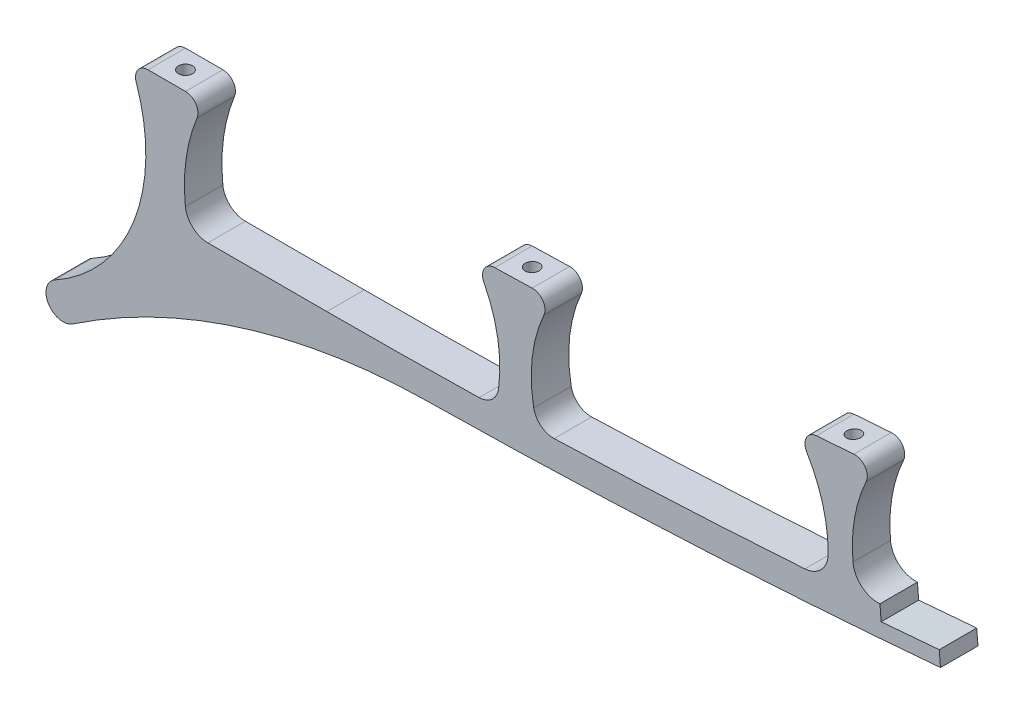
SolidWorks part; units mm, degrees
ref_plane "Front Plane" through (0, 0, 0) normal (0, 0, 1) x (1, 0, 0)
ref_plane "Top Plane" through (0, 0, 0) normal (0, 1, 0) x (1, 0, 0)
ref_plane "Right Plane" through (0, 0, 0) normal (1, 0, 0) x (0, 0, -1)
sketch "Sketch1" plane through (0, 0, 4.0971) normal (0, 0, -1) x (-1, 0, 0)
  line L0 (-62.7619, -51.7222) -> (-58.001, -51.5972) construction
  line L1 (-62.7619, -51.7222) -> (-58.001, -51.5972)
  line L2 (-250.1152, -63.0874) -> (-250.684, -56.8905) construction
  line L3 (-250.1152, -63.0874) -> (-250.684, -56.8905)
  line L4 (5.0134, -50.6875) -> (4.8506, -13.0704)
  line L5 (293.8258, -32.3629) -> (292.5411, -55.9947)
  line L6 (459.2981, -30.7507) -> (468.8231, -30.7507)
  line L7 (423.3798, -61.2307) -> (453.91, -61.2307)
  line L10 (423.2417, -37.1007) -> (607.4086, -37.1007) construction
  line L11 (270.0646, -24.076) -> (423.3798, -30.7507) construction
  line L12 (269.6518, -30.414) -> (423.1036, -37.0947) construction
  line L13 (270.0646, -24.076) -> (423.3798, -30.7507) construction
  line L14 (269.6518, -30.414) -> (423.2417, -37.1007) construction
  line L15 (270.0646, -24.076) -> (423.3798, -30.7507) construction
  line L16 (268.1133, -54.0366) -> (422.0742, -60.7394) construction
  line L17 (268.1133, -54.0366) -> (282.8559, -55.2703)
  line L39 (464.0606, -30.7507) -> (464.0606, -61.2307)
  line L43 (423.3798, -61.2307) -> (607.4086, -61.2307) construction
  line L44 (375.9837, -30.118) -> (375.1663, -60.587)
  line L45 (423.3798, -30.7507) -> (607.4086, -30.7507) construction
  arc A10 (295.9963, -50.7756) -> (301.9161, -57.1188) centre (302.3463, -50.7834) ccw
  arc A11 (301.4662, -31.1688) -> (298.9719, -26.3615) centre (298.7477, -29.5285) ccw
  arc A12 (289.4896, -25.6646) -> (286.3657, -30.1613) centre (289.2483, -28.8304) ccw
  arc A13 (282.8559, -55.2703) -> (289.7096, -49.5155) centre (283.3855, -48.9424) ccw
  arc A17 (301.4662, -31.1688) -> (295.9963, -50.7756) centre (334.0387, -50.8222) ccw
  arc A18 (289.7096, -49.5155) -> (286.3657, -30.1613) centre (251.8722, -46.0867) ccw
  circle A19 centre (490.3927, -92.6507) radius 4.3495
  arc A24 (383.4811, -34.8689) -> (379.749, -56.3925) centre (415.8403, -51.5652) ccw
  circle A29 centre (384.8064, -55.7161) radius 5.1024
  arc A30 (471.8244, -34.9614) -> (468.8231, -30.7507) centre (468.8231, -33.9257) ccw
  arc A31 (459.2981, -30.7507) -> (456.3562, -35.1198) centre (459.2981, -33.9257) ccw
  circle A32 centre (453.6208, -55.4881) radius 5.7427
  arc A33 (383.4811, -34.8689) -> (380.7361, -30.239) centre (380.6595, -33.4131) ccw
  arc A36 (459.3328, -56.0812) -> (456.3562, -35.1198) centre (415.8403, -51.5652) ccw
  arc A39 (368.2424, -34.4601) -> (371.2316, -29.9841) centre (371.1379, -33.1577) cw
  arc A40 (368.2424, -34.4601) -> (370.815, -56.1528) centre (335.0345, -49.3973) cw
  circle A41 centre (365.8012, -55.2062) radius 5.1024
  arc A42 (487.9615, -96.2573) -> (398.3517, -68.1968) centre (396.0818, -232.558) ccw
  arc A43 (471.8244, -34.9614) -> (492.4999, -88.8458) centre (514.2362, -49.5967) ccw
  spline S20 degree 1 poles (366398.024, 9576.3228) (-366524.7965, -9679.8002) knots -76971.699337 -76971.699337 76975.961644 76975.961644 only from (-53.2401, -51.4722) to (-58.001, -51.5972) construction
  spline S21 degree 1 poles (-53.2401, -51.4722) (-58.001, -51.5972) knots 0 0 1 1
  spline S22 degree 3 poles (-366283.8205, -17716.948) (-122202.6297, -5946.5803) (121970.8169, 5839.1835) (366052.004, 17609.5507) knots -76977.855707 -76977.855707 -76977.855707 -76977.855707 76982.000972 76982.000972 76982.000972 76982.000972 only from (-125.7663, -54.1741) to (-121.0093, -53.9446) construction
  spline S23 degree 1 poles (366035.5792, 17611.4947) (-366288.3596, -17719.9032) knots -76971.699337 -76971.699337 76975.961644 76975.961644 only from (-116.2524, -53.7151) to (-121.0093, -53.9446) construction
  spline S24 degree 3 poles (-125.7663, -54.1741) (-124.1807, -54.0976) (-122.595, -54.0211) (-121.0093, -53.9446) knots 0 0 0 0 1 1 1 1
  spline S25 degree 1 poles (-116.2524, -53.7151) (-121.0093, -53.9446) knots 0 0 1 1
  spline S26 degree 3 poles (-365864.3718, -25779.0387) (-122073.8662, -8605.5374) (121716.5905, 8490.9359) (365507.0964, 25664.4407) knots -76971.699337 -76971.699337 -76971.699337 -76971.699337 76975.961644 76975.961644 76975.961644 76975.961644 only from (-188.7625, -58.0119) to (-184.0117, -57.678) construction
  spline S27 degree 1 poles (365496.3363, 25644.4265) (-365875.1074, -25760.538) knots -76971.699337 -76971.699337 76975.961644 76975.961644 only from (-179.2609, -57.3441) to (-184.0117, -57.678) construction
  spline S28 degree 3 poles (-188.7625, -58.0119) (-187.1789, -57.9006) (-185.5953, -57.7893) (-184.0117, -57.678) knots 0 0 0 0 1 1 1 1
  spline S29 degree 1 poles (-179.2609, -57.3441) (-184.0117, -57.678) knots 0 0 1 1
  spline S30 degree 3 poles (-365301.3101, -33565.7342) (-121968.4672, -11235.1782) (121487.2779, 11110.751) (364820.1161, 33441.3066) knots -76979.795154 -76979.795154 -76979.795154 -76979.795154 76983.809836 76983.809836 76983.809836 76983.809836 only from (-250.1152, -63.0874) to (-245.3727, -62.6521) construction
  spline S31 degree 1 poles (364802.8942, 33440.7494) (-365304.3687, -33567.0383) knots -76971.699337 -76971.699337 76975.961644 76975.961644 only from (-240.6301, -62.2168) to (-245.3727, -62.6521) construction
  spline S32 degree 3 poles (-250.1152, -63.0874) (-248.5344, -62.9423) (-246.9535, -62.7972) (-245.3727, -62.6521) knots 0 0 0 0 1 1 1 1
  spline S33 degree 1 poles (-240.6301, -62.2168) (-245.3727, -62.6521) knots 0 0 1 1
  spline S34 degree 3 poles (-351120.2294, 74427.9388) (10494.0217, 34620.9522) (5972.352, 298.9935) (-6644.5567, -363.006) (-14732.5977, 33292.3398) (340712.2066, 110676.7005) knots -40.409558 -40.409558 -40.409558 -40.409558 0.498012 0.498012 41.40254 41.40254 41.40254 41.40254 only from (-260.2582, -26.3703) to (-413.5099, -34.3711) construction
  spline S35 degree 3 poles (-260.2582, -26.3703) (-285.573, -28.8027) (-310.9405, -30.6861) (-362.0399, -33.3672) (-387.7725, -34.1516) (-413.5099, -34.3711) knots 0.333333 0.333333 0.333333 0.333333 0.498012 0.498012 0.664679 0.664679 0.664679 0.664679
  spline S36 degree 3 poles (350477.0671, 77415.5224) (-10783.169, 34525.5553) (-5964.8095, 247.3458) (6657.3809, -305.4861) (14454.3598, 33422.1949) (-341643.6335, 107772.7294) knots -40.405514 -40.405514 -40.405514 -40.405514 0.5 0.5 41.406764 41.406764 41.406764 41.406764 only from (270.0646, -24.076) to (423.3798, -30.7507) construction
  spline S37 degree 3 poles (270.0646, -24.076) (295.3995, -26.2893) (320.7823, -27.9531) (371.903, -30.1921) (397.6415, -30.7539) (423.3798, -30.7507) knots 0.335321 0.335321 0.335321 0.335321 0.5 0.5 0.666667 0.666667 0.666667 0.666667
  spline S38 degree 3 poles (34216.6622, 363348.8873) (5327.7801, -4762.6903) (2936.3737, -226.3591) (225.9514, -20.5338) (214.915, -19.7614) (181.7932, -17.6233) (159.6926, -16.4536) (115.476, -14.6188) (93.3552, -13.9534) (60.1689, -13.3398) (49.1062, -13.195) (-2720.7868, 6.5962) (-5526.344, -4450.3222) (-4429.285, 364973.5107) knots -30.461707 -30.461707 -30.461707 -30.461707 0.125 0.125 0.25 0.25 0.5 0.5 0.75 0.75 0.875 0.875 32.045674 32.045674 32.045674 32.045674 only from (270.0646, -24.076) to (4.8506, -13.0704) construction
  spline S39 degree 3 poles (-37282.4943, 363051.1607) (-5277.6718, -4808.7913) (-2924.7638, -251.7198) (-216.1773, -22.4465) (-205.1481, -21.5787) (-172.0462, -19.1541) (-149.9564, -17.7933) (-105.7573, -15.5759) (-83.6432, -14.7191) (-50.4634, -13.8184) (-39.4023, -13.5779) (2730.1506, 30.1779) (5573.6801, -4402.0973) (1314.8646, 364983.8749) knots -30.462296 -30.462296 -30.462296 -30.462296 0.125 0.125 0.25 0.25 0.5 0.5 0.75 0.75 0.875 0.875 32.044896 32.044896 32.044896 32.044896 only from (-260.2582, -26.3703) to (4.8506, -13.0704) construction
  spline S40 degree 3 poles (270.0646, -24.076) (259.0414, -23.1193) (248.0148, -22.2092) (225.9514, -20.5338) (214.915, -19.7614) (181.7932, -17.6233) (159.6926, -16.4536) (115.476, -14.6188) (93.3552, -13.9534) (60.1689, -13.3398) (49.1062, -13.195) (26.9794, -13.0369) (15.9153, -13.0299) (4.8506, -13.0704) knots 0 0 0 0 0.125 0.125 0.25 0.25 0.5 0.5 0.75 0.75 0.875 0.875 1 1 1 1
  spline S41 degree 3 poles (-260.2582, -26.3703) (-249.2437, -25.3183) (-238.2254, -24.3128) (-216.1773, -22.4465) (-205.1481, -21.5787) (-172.0462, -19.1541) (-149.9564, -17.7933) (-105.7573, -15.5759) (-83.6432, -14.7191) (-50.4634, -13.8184) (-39.4023, -13.5779) (-17.2777, -13.2284) (-6.214, -13.1256) (4.8506, -13.0704) knots 0 0 0 0 0.125 0.125 0.25 0.25 0.5 0.5 0.75 0.75 0.875 0.875 1 1 1 1
  spline S42 degree 1 poles (266.8016, -61.5516) (423.3844, -68.3681) knots 0 0 1 1 construction
  spline S43 degree 1 poles (266.8016, -61.5516) (5.0134, -50.6875) knots 0 0 1 1 construction
  spline S44 degree 1 poles (-256.671, -63.8163) (5.0134, -50.6875) knots 0 0 1 1 construction
  spline S45 degree 1 poles (-256.671, -63.8163) (-413.1891, -71.9871) knots 0 0 1 1 construction
  spline S46 degree 3 poles (423.3844, -68.3681) (417.128, -68.3689) (406.6951, -68.3157) (354.4413, -67.5941) (308.4593, -65.1906) (266.8016, -61.5516) knots 0.335344 0.335344 0.335344 0.335344 0.375021 0.401473 0.666667 0.666667 0.666667 0.666667
  spline S47 degree 3 poles (266.8016, -61.5516) (261.3509, -61.0786) (250.4335, -60.154) (228.7012, -58.4345) (190.549, -55.7631) (136.0425, -52.8693) (81.4825, -51.2368) (43.241, -50.7379) (21.4384, -50.6506) (10.4839, -50.6675) (5.0134, -50.6875) knots 0.00004 0.00004 0.00004 0.00004 0.062532 0.125024 0.250007 0.499973 0.749939 0.874922 0.937414 0.999905 0.999905 0.999905 0.999905
  spline S48 degree 3 poles (5.0134, -50.6875) (-0.4572, -50.7148) (-11.4114, -50.7928) (-33.2124, -51.0686) (-71.4483, -51.8985) (-125.9921, -54.0029) (-180.4716, -57.3683) (-218.5991, -60.3696) (-240.3157, -62.2771) (-251.2247, -63.2961) (-256.671, -63.8163) knots 0.00004 0.00004 0.00004 0.00004 0.062532 0.125023 0.250007 0.499973 0.749939 0.874922 0.937414 0.999905 0.999905 0.999905 0.999905
  spline S49 degree 3 poles (-256.671, -63.8163) (-308.6753, -68.8128) (-360.9473, -71.5416) (-413.1891, -71.9871) knots 0.333356 0.333356 0.333356 0.333356 0.664679 0.664679 0.664679 0.664679
  spline S50 degree 1 poles (267.412, -54.4403) (423.3798, -61.2307) knots 0 0 1 1 construction
  spline S51 degree 1 poles (268.1133, -54.0366) (4.9805, -43.0872) knots 0 0 1 1 construction
  spline S52 degree 1 poles (-257.3958, -56.2506) (4.9805, -43.0872) knots 0 0 1 1 construction
  spline S53 degree 1 poles (-257.3958, -56.2506) (-413.254, -64.3871) knots 0 0 1 1 construction
  spline S54 degree 3 poles (267.412, -54.4403) (276.0285, -55.1931) (290.4062, -56.3442) (313.5674, -57.917) (336.8899, -59.2149) (356.0529, -59.9983) (367.2252, -60.3576) (370.4015, -60.4534) (373.5779, -60.5449) (376.7545, -60.6301) (379.9313, -60.709) (383.1082, -60.7837) (397.5889, -61.095) (411.2827, -61.2322) (423.3798, -61.2307) knots 0.335321 0.335321 0.335321 0.335321 0.390393 0.427108 0.483088 0.539068 0.549181 0.554238 0.559295 0.569408 0.574465 0.579521 0.589635 0.666659 0.666659 0.666659 0.666659 only from (301.9161, -57.1188) to (423.3798, -61.2307)
  spline S55 degree 3 poles (268.1133, -54.0366) (262.6347, -53.5611) (251.6633, -52.6287) (229.8118, -50.8954) (191.4718, -48.2039) (136.6796, -45.2869) (81.8357, -43.6415) (43.4028, -43.1385) (21.4808, -43.0503) (10.477, -43.0671) (4.9805, -43.0872) knots -0.002434 -0.002434 -0.002434 -0.002434 0.060213 0.122861 0.248155 0.498745 0.749335 0.87463 0.937277 0.999924 0.999924 0.999924 0.999924
  spline S56 degree 3 poles (4.9805, -43.0872) (-0.5025, -43.1146) (-11.479, -43.1927) (-33.3456, -43.4694) (-71.6781, -44.3013) (-126.3714, -46.4114) (-181.0006, -49.7861) (-219.224, -52.795) (-241.0064, -54.7082) (-251.9372, -55.7293) (-257.3958, -56.2506) knots 0.000032 0.000032 0.000032 0.000032 0.062525 0.125019 0.250005 0.499978 0.749951 0.874938 0.937431 0.999924 0.999924 0.999924 0.999924
  spline S57 degree 3 poles (-257.3958, -56.2506) (-309.1808, -61.2261) (-361.2324, -63.9435) (-413.254, -64.3871) knots 0.333351 0.333351 0.333351 0.333351 0.664679 0.664679 0.664679 0.664679
  spline S59 degree 3 poles (-413.1844, -71.9874) (-456.1014, -80.1224) (-434.4954, -79.3287) (-479.9907, -101.3371) (-478.4868, -100.9323) knots 0 0 0 0 0.938514 1 1 1 1
  spline S61 degree 1 poles (269.6518, -30.414) (4.8739, -19.4204) knots 0 0 1 1 construction
  spline S63 degree 3 poles (4.8739, -19.4204) (26.9656, -19.3394) (71.1539, -19.6344) (137.3995, -21.6337) (203.5831, -25.1323) (247.6429, -28.5039) (269.6518, -30.414) knots -0.000515 -0.000515 -0.000515 -0.000515 0.249614 0.499743 0.749871 1 1 1 1
  spline S66 degree 1 poles (269.6518, -30.414) (4.8739, -19.4204) knots 0 0 1 1 construction
  spline S68 degree 3 poles (4.8739, -19.4204) (26.9656, -19.3394) (71.1539, -19.6344) (137.3995, -21.6337) (203.5831, -25.1323) (247.6429, -28.5039) (269.6518, -30.414) knots -0.000515 -0.000515 -0.000515 -0.000515 0.249614 0.499743 0.749871 1 1 1 1
  point P81 (310.3019, -33.4897)
  dimension "D3" = 30.48
  dimension "D5" = 6.35
  dimension "D8" = 4.7625
  dimension "D9" = 3.175
  dimension "D10" = 9.525
  dimension "D11" = 12.7
  dimension "D12" = 19.05
  dimension "D16" = 12.7
  dimension "D17" = 3.175
  dimension "D18" = 4.7625
  dimension "D19" = 4.7625
  dimension "D13" = 9.525
  dimension "D14" = 4.7625
  dimension "D15" = 25.4
  dimension "D1" = 37.6174
  dimension "D7" = 6.35
  dimension "D22" = 6.35
extrude "Boss-Extrude5" add sketch "Sketch1" along normal blind 4.7625 and the other way blind 4.7625 contours L7 S54 A10 A17 A11 S37 A12 A18 A13 L17 S55 | A19 | A19 | S54 L44 S37 | L44 S54 A29 A24 A33 S37 region at (-287.273, -56.7987, 4.0971) region at (-490.3927, -92.6507, 4.0971) region at (-372.7453, -43.9651, 4.0971) region at (-378.475, -44.1188, 4.0971)
ref_plane "Plane1" through (0.3209, -4.3662, 0) normal (-0.0733, 0.9973, 0) x (0.9973, 0.0733, 0)
sketch "Sketch6" plane through (0.3209, -4.3662, 0) normal (-0.0733, 0.9973, 0) x (0.9973, 0.0733, 0)
  line L0 (-295.346, 0.6654) -> (-295.346, -8.8596) construction
  line L1 (-290.592, -4.0971) -> (-300.0999, -4.0971) construction
  line L4 (-290.592, -8.8596) -> (-290.592, 0.6654)
  line L10 (-300.0999, 0.6654) -> (-300.0999, -8.8596)
  line L24 (-290.592, -8.8596) -> (-290.592, 0.6654)
  line L27 (-290.592, 0.6654) -> (-300.0999, 0.6654)
  line L29 (-290.592, 0.6654) -> (-300.0999, 0.6654)
  line L30 (-300.0999, -8.8596) -> (-290.592, -8.8596)
  line L31 (-300.0999, -8.8596) -> (-290.592, -8.8596)
  line L34 (-300.0999, 0.6654) -> (-300.0999, -8.8596)
  circle A0 centre (-295.346, -4.0971) radius 1.778
  point P6 (-290.592, -4.0971)
  point P7 (-295.346, 0.6654)
  point P12 (0, 0)
  point P13 (-295.346, -4.0971)
  dimension "D1" = 0
extrude "Cut-Extrude3" cut sketch "Sketch6" against normal through all contours A0
ref_axis "Axis1" through (-291.4807, -63.4328, 4.0971) along (-0.0733, 0.9973, 0)
ref_plane "Plane2" through (3.0659, -41.7188, 0) normal (-0.0733, 0.9973, 0) x (-0.9947, -0.0731, 0.0729)
sketch "Sketch7" plane through (3.0659, -41.7188, 0) normal (-0.0733, 0.9973, 0) x (-0.9947, -0.0731, 0.0729)
  circle A0 centre (294.8582, -17.4541) radius 1.778 construction
  circle A1 centre (294.8582, -17.4541) radius 1.778
  circle A2 centre (294.8582, -17.4541) radius 3.048
  dimension "D1" = 6.096
extrude "Cut-Extrude4" cut sketch "Sketch7" along normal blind 3.556 and the other way through all
mirror "Mirror4" about plane through (-4.794, 0.0207, 8.8596) normal (-1, 0.0043, 0) of "Cut-Extrude4", "Cut-Extrude3", "Boss-Extrude5"
sketch "Sketch8" plane through (0, 0, -0.6654) normal (0, 0, -1) x (-1, 0, 0)
  line L0 (-4352.3873, -105.2388) -> (-4674.1378, -106.5977)
  line L1 (-4352.3873, -105.2388) -> (-4352.7091, -29.0388)
  line L2 (-4674.1378, -106.5977) -> (-4674.4596, -30.3977)
  line L3 (-4352.7091, -29.0388) -> (-4674.4596, -30.3977)
  dimension "D1" = 76.2
  dimension "D2" = 321.7505
sketch "Sketch9" plane through (0, 0, -0.6654) normal (0, 0, -1) x (-1, 0, 0)
  line L0 (268.1133, -54.0366) -> (282.8559, -55.2703) construction
  line L1 (268.1133, -54.0366) -> (282.8559, -55.2703)
  line L2 (267.7955, -57.8333) -> (282.5382, -59.067)
  line L3 (282.5382, -59.067) -> (282.8559, -55.2703)
  line L4 (267.7955, -57.8333) -> (267.4671, -61.6096)
  line L5 (268.1133, -54.0366) -> (271.2267, -16.8305)
  line L6 (271.2267, -16.8305) -> (-501.7302, -16.8305)
  line L7 (-501.7302, -16.8305) -> (-501.7302, -147.1798)
  line L8 (-501.7302, -147.1798) -> (267.4671, -61.6096)
  spline S0 degree 3 poles (2340.1552, 397.7315) (1297.6129, 87.0856) (115.0439, -338.026) (-1058.2174, 398.7267) (-1032.0079, 1250.0528) knots -2.465055 -2.465055 -2.465055 -2.465055 0.401473 5.010775 5.010775 5.010775 5.010775 only from (398.3517, -68.1968) to (266.8016, -61.5516) construction
  spline S1 degree 3 poles (398.3517, -68.1968) (396.2658, -68.168) (352.3561, -67.4851) (308.4593, -65.1906) (266.8016, -61.5516) knots 0.388247 0.388247 0.388247 0.388247 0.401473 0.666667 0.666667 0.666667 0.666667
  dimension "D1" = 3.81
extrude "Cut-Extrude5" cut sketch "Sketch9" against normal through all contours L7 L8 L4 L2 L3 L1 L5 L6 region at (178.8306, -64.0501, -0.6654)
ref_plane "Plane3" through (0.5368, -20.0102, 0) normal (-0.0268, 0.9996, 0) x (0.9996, 0.0268, 0)
sketch "Sketch10" plane through (0.5368, -20.0102, 0) normal (-0.0268, 0.9996, 0) x (0.9996, 0.0268, 0)
  line L0 (-376.6562, 0.6654) -> (-376.6562, -8.8596) construction
  line L1 (-371.9023, -4.0971) -> (-381.4101, -4.0971) construction
  line L4 (-371.9023, -8.8596) -> (-371.9023, 0.6654)
  line L5 (-371.9023, 0.6654) -> (-381.4101, 0.6654)
  line L6 (-381.4101, 0.6654) -> (-381.4101, -8.8596)
  line L7 (-381.4101, -8.8596) -> (-371.9023, -8.8596)
  line L8 (-371.9023, -8.8596) -> (-371.9023, 0.6654)
  line L9 (-371.9023, 0.6654) -> (-381.4101, 0.6654)
  line L10 (-381.4101, 0.6654) -> (-381.4101, -8.8596)
  line L11 (-381.4101, -8.8596) -> (-371.9023, -8.8596)
  circle A0 centre (-376.6562, -4.0971) radius 1.778
  dimension "D1" = 0
extrude "Cut-Extrude6" cut sketch "Sketch10" against normal through all contours A0 region at (-375.9839, -30.1115, 4.0971)
ref_point "Point1"
ref_plane "Plane5" through (1.5458, -57.6195, 0) normal (-0.0268, 0.9996, 0) x (0.9996, 0.0268, 0)
sketch "Sketch12" plane through (1.5458, -57.6195, 0) normal (-0.0268, 0.9996, 0) x (0.9996, 0.0268, 0)
  circle A2 centre (-376.6562, -4.0971) radius 3.048
  dimension "D1" = 6.096
extrude "Cut-Extrude11" cut sketch "Sketch12" along normal blind 3.556 and the other way through all contours A2
ref_plane "Plane6" through (0, -30.7507, 0) normal (0, 1, 0) x (1, 0, 0)
sketch "Sketch13" plane through (0, -30.7507, 0) normal (0, 1, 0) x (1, 0, 0)
  line L0 (-464.0606, 0.6654) -> (-464.0606, -8.8596) construction
  line L1 (-459.2981, -4.0971) -> (-468.8231, -4.0971) construction
  line L4 (-459.2981, -8.8596) -> (-459.2981, 0.6654)
  line L5 (-459.2981, 0.6654) -> (-468.8231, 0.6654)
  line L6 (-468.8231, 0.6654) -> (-468.8231, -8.8596)
  line L7 (-468.8231, -8.8596) -> (-459.2981, -8.8596)
  line L8 (-459.2981, -8.8596) -> (-459.2981, 0.6654)
  line L9 (-459.2981, 0.6654) -> (-468.8231, 0.6654)
  line L10 (-468.8231, 0.6654) -> (-468.8231, -8.8596)
  line L11 (-468.8231, -8.8596) -> (-459.2981, -8.8596)
  circle A0 centre (-464.0606, -4.0971) radius 1.778
  dimension "D1" = 0
extrude "Cut-Extrude12" cut sketch "Sketch13" against normal through all contours A0 region at (-464.0606, -30.7507, 4.0971)
ref_plane "Plane7" through (0, -68.8507, 0) normal (0, 1, 0) x (1, 0, 0)
sketch "Sketch14" plane through (0, -68.8507, 0) normal (0, 1, 0) x (1, 0, 0)
  circle A2 centre (-464.0606, -4.0971) radius 3.048
  dimension "D1" = 6.096
extrude "Cut-Extrude13" cut sketch "Sketch14" along normal blind 3.556 and the other way through all
ref_plane "Plane8" through (0, 0, 4.0971) normal (0, 0, -1) x (-1, 0, 0)
